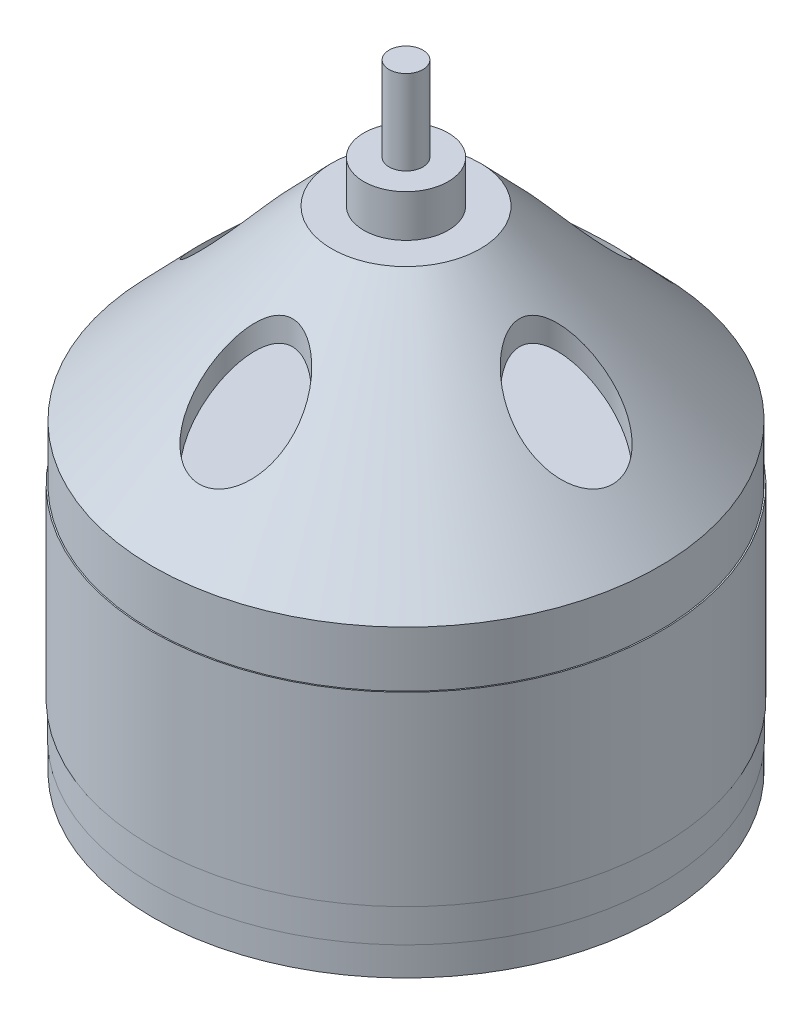
SolidWorks part; units mm, degrees
ref_plane "Alzado" through (0, 0, 0) normal (0, 0, 1) x (1, 0, 0)
ref_plane "Planta" through (0, 0, 0) normal (0, 1, 0) x (1, 0, 0)
ref_plane "Vista lateral" through (0, 0, 0) normal (1, 0, 0) x (0, 0, -1)
sketch "Croquis2" plane through (0, 0, 0) normal (1, 0, 0) x (0, 0, -1)
  line L0 (0, -9.2129) -> (15, -9.2129)
  line L1 (0, 55) -> (0, -55) construction
  line L2 (15, -9.2129) -> (15, 8.7871)
  line L3 (15, 8.7871) -> (4.4005, 19.7886)
  line L4 (4.4005, 19.7886) -> (0, 19.7886)
  line L5 (0, -10.6647) -> (0, 25.7599) construction
  line L6 (0, 19.7886) -> (0, -9.2129)
revolve "Revolución1" add sketch "Croquis2" angle 360 about L5
sketch "Croquis3" plane through (0, 19.7886, 0) normal (0, 1, 0) x (1, 0, 0)
  circle A0 centre (0, 0) radius 2.5
extrude "Saliente-Extruir1" add sketch "Croquis3" along normal blind 2.5
sketch "Croquis4" plane through (0, 22.2886, 0) normal (0, 1, 0) x (1, 0, 0)
  circle A0 centre (0, 0) radius 1
extrude "Saliente-Extruir2" add sketch "Croquis4" along normal blind 5
shell "Vaciado1" thickness 1 removed face at (0, -9.2129, -15)
sketch "Croquis6" plane through (0, 19.7886, 0) normal (0, 1, 0) x (1, 0, 0)
  line L0 (0, -16.5) -> (0, 16.5) construction
  circle A0 centre (0, -9.4879) radius 2.7609
  circle A1 centre (-9.4879, 0) radius 2.7609
  circle A2 centre (0, 9.4879) radius 2.7609
  circle A3 centre (9.4879, 0) radius 2.7609
  dimension "D1" = 4
extrude "Cortar-Extruir1" cut sketch "Croquis6" against normal blind 35
sketch "Croquis7" plane through (0, -9.2129, 0) normal (0, -1, 0) x (1, 0, 0)
  circle A0 centre (0, 0) radius 14
extrude "Saliente-Extruir3" add sketch "Croquis7" against normal blind 1
sketch "Croquis8" plane through (0, 0, 0) normal (0, 1, 0) x (1, 0, 0)
  circle A0 centre (0, 0) radius 15.0755
extrude "Saliente-Extruir4" add sketch "Croquis8" along normal mid plane 11
sketch "Croquis9" plane through (0, -5.5, 0) normal (0, -1, 0) x (1, 0, 0)
  circle A0 centre (0, 0) radius 15.0228
extrude "Saliente-Extruir5" add sketch "Croquis9" along normal blind 2
